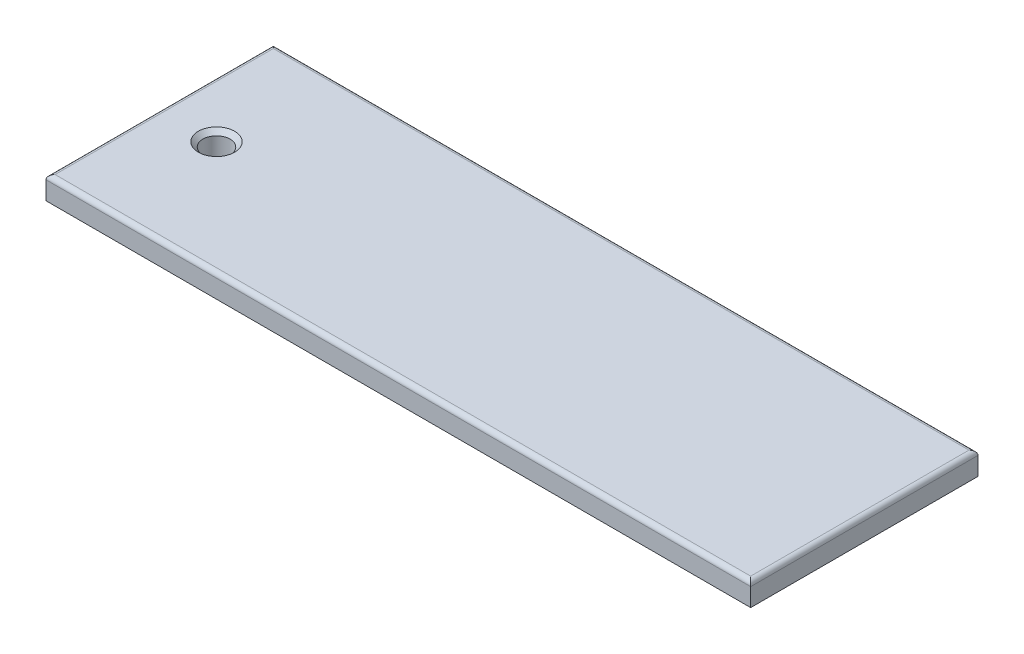
SolidWorks part; units mm, degrees
ref_plane "Front Plane" through (0, 0, 0) normal (0, 0, 1) x (1, 0, 0)
ref_plane "Top Plane" through (0, 0, 0) normal (0, 1, 0) x (1, 0, 0)
ref_plane "Right Plane" through (0, 0, 0) normal (1, 0, 0) x (0, 0, -1)
sketch "Sketch1" plane through (0, 0, 0) normal (0, 1, 0) x (1, 0, 0)
  line L1 (155, -50) -> (-155, -50)
  line L2 (155, -50) -> (155, 50)
  line L3 (155, 50) -> (-155, 50)
  line L4 (-155, -50) -> (-155, 50)
  line L5 (0, 50) -> (0, -50) construction
  line L6 (155, 0) -> (-155, 0) construction
  point P0 (0, 0)
  dimension "D1" = 310
  dimension "D2" = 100
extrude "Boss-Extrude1" add sketch "Sketch1" along normal blind 10
fillet "Fillet1" radius 2 4 edges at (-155, 10, 0) (0, 10, -50) (155, 10, 0) (0, 10, 50)
sketch "Sketch2" plane through (0, 10, 0) normal (0, 1, 0) x (1, 0, 0)
  line L0 (-155, -50) -> (-155, 50) construction
  circle A0 centre (-130, 0) radius 6
  dimension "D2" = 12
  dimension "D1" = 25
extrude "Cut-Extrude1" cut sketch "Sketch2" against normal through all
chamfer "Chamfer1" distance 2 angle 45 1 edges at (-130, 10, 6)
